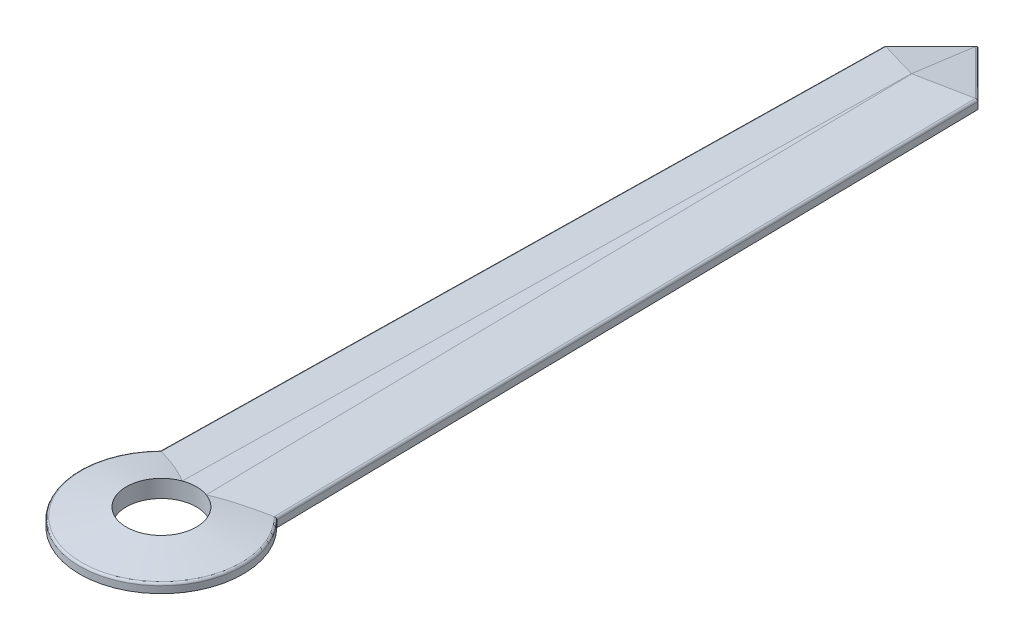
SolidWorks part; units mm, degrees
ref_plane "Front Plane" through (0, 0, 0) normal (0, 0, 1) x (1, 0, 0)
ref_plane "Top Plane" through (0, 0, 0) normal (0, 1, 0) x (1, 0, 0)
ref_plane "Right Plane" through (0, 0, 0) normal (1, 0, 0) x (0, 0, -1)
sketch "Sketch1" plane through (0, 0, 0) normal (0, 1, 0) x (1, 0, 0)
  line L0 (-0.635, 0.6222) -> (-0.508, 8.382)
  line L1 (-0.508, 8.382) -> (0, 8.89)
  line L2 (0, 8.89) -> (0.508, 8.382)
  line L6 (0.508, 8.382) -> (0.635, 0.6222)
  circle A0 centre (0, 0) radius 0.381
  arc A1 (-0.635, 0.6222) -> (0.635, 0.6222) centre (0, 0) ccw
  dimension "D1" = 0.762
  dimension "D2" = 1.778
  dimension "D3" = 1.27
  dimension "D4" = 8.89
  dimension "D5" = 0.508
  dimension "D6" = 0.508
  dimension "D7" = 0.508
extrude "Extrude1" add sketch "Sketch1" along normal blind 0.1905
chamfer "Chamfer3" distance 0.0953 angle 79.4 5 edges at (0, 0.1905, 0.889) (0.5715, 0.1905, -4.5021) (0.254, 0.1905, -8.636) (-0.254, 0.1905, -8.636) (-0.5715, 0.1905, -4.5021) first distance on face at (0, 0.0953, 0.1334) first distance on face at (0.5715, 0.0953, -4.5021) first distance on face at (0.254, 0.0953, -8.636) first distance on face at (-0.254, 0.0953, -8.636) first distance on face at (-0.5715, 0.0953, -4.5021)
fillet "Fillet5" radius 0.0254 5 edges at (0.254, 0.0952, -8.636) (-0.254, 0.0952, -8.636) (0.5715, 0.0952, -4.5021) (-0.5715, 0.0952, -4.5021) (0, 0.0952, 0.889)
